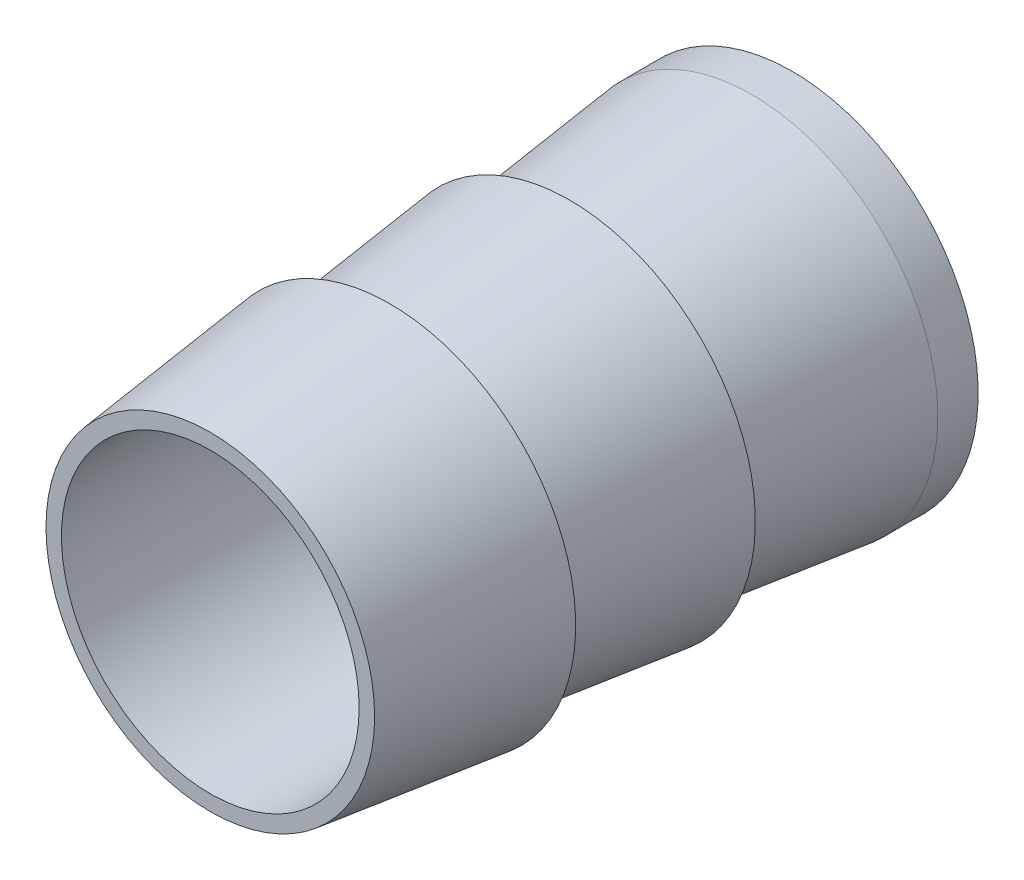
SolidWorks part; units mm, degrees
ref_plane "Front Plane" through (0, 0, 0) normal (0, 0, 1) x (1, 0, 0)
ref_plane "Top Plane" through (0, 0, 0) normal (0, 1, 0) x (1, 0, 0)
ref_plane "Right Plane" through (0, 0, 0) normal (1, 0, 0) x (0, 0, -1)
sketch "Sketch2" plane through (0, 0, 0) normal (1, 0, 0) x (0, 0, -1)
  line L0 (8.7392, 0) -> (-6.1547, 0)
  line L1 (8.7392, 0) -> (15.2797, 0) construction
  line L2 (-6.1547, 0) -> (-6.1547, 4.2059)
  line L15 (-6.0056, 4.2237) -> (-1.5549, 4.7536)
  line L16 (-1.5549, 4.7536) -> (-1.5549, 4.2059)
  line L20 (-1.4058, 4.2237) -> (3.0449, 4.7536)
  line L23 (3.0449, 4.7536) -> (3.0449, 4.2059)
  line L24 (3.194, 4.2237) -> (7.708, 4.7612)
  line L27 (7.708, 4.7612) -> (8.7392, 4.7625)
  line L30 (-6.0056, 4.2237) -> (-6.1547, 4.2059)
  line L31 (-1.4058, 4.2237) -> (-1.5549, 4.2059)
  line L32 (3.194, 4.2237) -> (3.0449, 4.2059)
  line L33 (8.7392, 4.7625) -> (8.7392, 0)
revolve "Barbfitting(Mcmaster)" add sketch "Sketch2" angle 360 about L0
sketch "Sketch3" plane through (0, 0, 6.1547) normal (0, 0, 1) x (1, 0, 0)
  circle A0 centre (0, 0) radius 3.81
  dimension "D1" = 7.62
extrude "Cut-Extrude1" cut sketch "Sketch3" against normal through all
